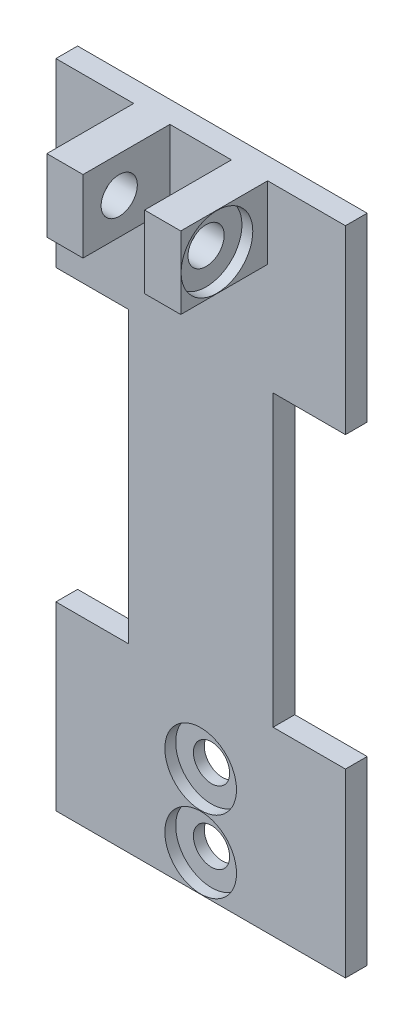
SolidWorks part; units mm, degrees
ref_plane "Front Plane" through (0, 0, 0) normal (0, 0, 1) x (1, 0, 0)
ref_plane "Top Plane" through (0, 0, 0) normal (0, 1, 0) x (1, 0, 0)
ref_plane "Right Plane" through (0, 0, 0) normal (1, 0, 0) x (0, 0, -1)
sketch "Sketch1" plane through (0, 0, 0) normal (0, 0, 1) x (1, 0, 0)
  line L0 (-14.0259, 75.3035) -> (-14.0259, -14.6965) construction
  line L1 (-34.0259, 75.3035) -> (5.9741, 75.3035)
  line L2 (-34.0259, 75.3035) -> (-34.0259, -14.6965)
  line L3 (-34.0259, -14.6965) -> (5.9741, -14.6965)
  line L4 (5.9741, 75.3035) -> (5.9741, -14.6965)
  line L5 (-24.0259, 30.3035) -> (-34.0259, 30.3035) construction
  line L6 (-34.0259, 50.3035) -> (-24.0259, 50.3035)
  line L7 (-34.0259, 50.3035) -> (-34.0259, 10.3035)
  line L8 (-34.0259, 10.3035) -> (-24.0259, 10.3035)
  line L9 (-24.0259, 50.3035) -> (-24.0259, 10.3035)
  line L10 (5.9741, 30.3035) -> (-34.0259, 30.3035) construction
  line L11 (5.9741, 50.3035) -> (-4.0259, 50.3035)
  line L12 (-4.0259, 50.3035) -> (-4.0259, 10.3035)
  line L13 (5.9741, 10.3035) -> (-4.0259, 10.3035)
  line L14 (-14.0259, 65.3035) -> (-14.0259, 75.3035) construction
  line L15 (-18.2759, 75.3035) -> (-9.7759, 75.3035)
  line L16 (-18.2759, 75.3035) -> (-18.2759, 65.3035)
  line L17 (-18.2759, 65.3035) -> (-9.7759, 65.3035)
  line L18 (-9.7759, 75.3035) -> (-9.7759, 65.3035)
  line L20 (-18.2759, 65.3035) -> (-23.2759, 65.3035)
  line L21 (-18.2759, 65.3035) -> (-18.2759, 75.3035)
  line L22 (-18.2759, 75.3035) -> (-23.2759, 75.3035)
  line L23 (-23.2759, 65.3035) -> (-23.2759, 75.3035)
  line L24 (-9.7759, 65.3035) -> (-4.7759, 65.3035)
  line L25 (-9.7759, 65.3035) -> (-9.7759, 75.3035)
  line L26 (-9.7759, 75.3035) -> (-4.7759, 75.3035)
  line L27 (-4.7759, 65.3035) -> (-4.7759, 75.3035)
  circle A0 centre (-14.0259, -9.6965) radius 2.5
  circle A1 centre (-14.0259, 0.3035) radius 2.5
  circle A2 centre (-14.0259, 0.3035) radius 4.95
  circle A3 centre (-14.0259, -9.6965) radius 4.95
  dimension "D3" = 5
  dimension "D4" = 5
  dimension "D5" = 9.9
  dimension "D6" = 9.9
  dimension "D1" = 90
  dimension "D2" = 40
  dimension "D7" = 5
  dimension "D8" = 15
  dimension "D9" = 40
  dimension "D10" = 10
  dimension "D11" = 10
  dimension "D12" = 8.5
  dimension "D13" = 5
  dimension "D14" = 5
extrude "Body" add sketch "Sketch1" along normal blind 3 contours L27 L24 L17 L20 L23 L1 L2 L6 L9 L8 L3 L4 L13 L12 L11 A3 A2 | L23 L20 L16 L1 | L18 L1 L16 L17 | L24 L27 L1 L18 region at (-14.0259, 29.4861, 0) region at (-20.7759, 70.3035, 0) region at (-14.0259, 70.3035, 0) region at (-7.2759, 70.3035, 0)
extrude "Mount Insets" add sketch "Sketch1<3>" along normal blind 1.5 contours A2 A1 | A3 A0 region at (-18.8359, 0.3035, 0) region at (-18.8359, -9.6965, 0)
sketch "Sketch1<3>" plane through (0, 0, 0) normal (0, 0, 1) x (1, 0, 0) same geometry as "Sketch1"
extrude "Hinge" add sketch "Sketch1<5>" along normal blind 15 contours L24 L27 L1 L18 | L20 L23 L22 L21 region at (-7.2759, 70.3035, 0)
sketch "Sketch1<5>" plane through (0, 0, 0) normal (0, 0, 1) x (1, 0, 0) same geometry as "Sketch1"
sketch "Sketch2" plane through (-4.7759, 0, 0) normal (1, 0, 0) x (0, 0, -1)
  line L0 (-15, 70.3035) -> (-3, 70.3035) construction
  line L1 (-15, 65.3035) -> (-15, 75.3035) construction
  line L2 (-3, 75.3035) -> (-3, 65.3035) construction
  line L3 (-10, 75.3035) -> (-10, 65.3035) construction
  line L4 (-15, 75.3035) -> (-3, 75.3035) construction
  line L5 (-15, 65.3035) -> (-3, 65.3035) construction
  circle A0 centre (-10, 70.3035) radius 2.5
  circle A1 centre (-10, 70.3035) radius 4.95
  dimension "D2" = 5
  dimension "D3" = 9.9
  dimension "D1" = 5
extrude "Hinge Inset" cut sketch "Sketch2" against normal blind 1.5
extrude "Hinge Inset2" cut sketch "Sketch2<2>" along normal blind 1.5 from surface starting at face at (-23.2759, 70.3035, 9)
sketch "Sketch2<2>" plane through (-4.7759, 0, 0) normal (1, 0, 0) x (0, 0, -1) same geometry as "Sketch2"
extrude "Hinge Screwhole" cut sketch "Sketch2<3>" against normal through all contours A0 region at (-4.7759, 70.3035, 10)
sketch "Sketch2<3>" plane through (-4.7759, 0, 0) normal (1, 0, 0) x (0, 0, -1) same geometry as "Sketch2"
